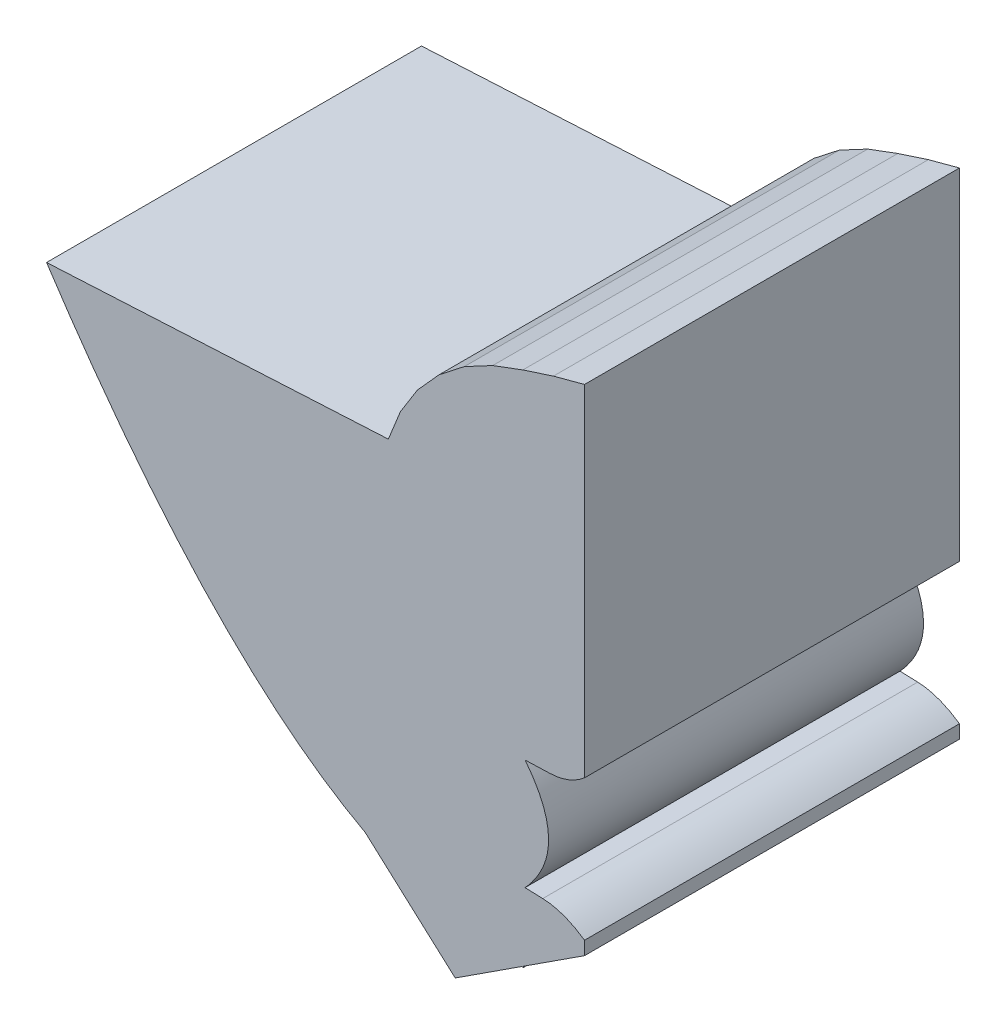
SolidWorks part; units mm, degrees
ref_plane "Alzado" through (0, 0, 0) normal (0, 0, 1) x (1, 0, 0)
ref_plane "Planta" through (0, 0, 0) normal (0, 1, 0) x (1, 0, 0)
ref_plane "Vista lateral" through (0, 0, 0) normal (1, 0, 0) x (0, 0, -1)
sketch "Croquis1" plane through (0, 0, 0) normal (0, 0, 1) x (1, 0, 0)
  line L0 (-8.9818, 12.6082) -> (-23.0359, 11.8716) construction
  line L1 (-8.9818, 12.6082) -> (-23.0359, 11.8716)
  line L2 (-8.9818, 12.6082) -> (-23.0359, 11.8716) construction
  line L3 (-2.1773, 6.1864) -> (-2.1773, -4.6845)
  line L4 (-8.9818, 12.6082) -> (-23.0359, 11.8716)
  line L6 (-1.3949, 1.9763) -> (0.3551, 2.2848) construction
  line L7 (-1.3949, 1.9763) -> (0.3551, 2.2848) construction
  line L8 (0.3551, 2.2848) -> (0.3551, 2.8423) construction
  line L9 (0.3551, 2.2848) -> (0.3551, 3.0015) construction
  line L10 (0.3551, -2.2848) -> (-1.3949, -2.2237) construction
  line L11 (0.3551, -2.2848) -> (-1.3949, -2.2237) construction
  line L12 (0.3551, 2.2848) -> (0.3551, -2.2848) construction
  line L13 (0.3551, -2.2848) -> (0.3551, -2.7233) construction
  line L14 (-8.9818, 12.6082) -> (-6.9949, 10.4774)
  line L15 (-23.0359, 11.5401) -> (-23.0359, 11.8716) construction
  line L16 (-23.0359, 11.5401) -> (-23.0359, 11.8716)
  arc A0 (-18.9452, 7.5409) -> (-23.0359, 11.5401) centre (-69.8841, -40.4718) ccw construction
  arc A1 (-18.9452, 7.5409) -> (-23.0359, 11.5401) centre (-69.8841, -40.4718) ccw
  spline S1 degree 2 poles (-4119.0151, 24659.0515) (3413.1083, -24757.661) (-2705.4818, 24835.5983) knots 0.405517 0.405517 0.405517 0.594449 0.594449 0.594449 weights 1 1 1 only from (-18.9452, 7.5409) to (-2.8466, -5.0591) construction
  spline S2 degree 2 poles (-18.9452, 7.5409) (-10.215, -3.6976) (-2.8466, -5.0591) knots 0.497667 0.497667 0.497667 0.499554 0.499554 0.499554 weights 1 1 1
  spline S3 degree 2 poles (-23607.9882, 8212.1168) (23492.4763, -8550.6979) (-23372.6553, 8887.1675) knots 0.40552 0.40552 0.40552 0.594498 0.594498 0.594498 weights 1 1 1 only from (0.3551, 3.0015) to (-6.9949, 10.4774) construction
  spline S4 degree 2 poles (-2.1773, 6.1864) (-4.0633, 8.1416) (-6.9949, 10.4774) knots 0.501383 0.501383 0.501383 0.502013 0.502013 0.502013 weights 1 1 1
  spline S5 degree 2 poles (-1.3949, -2.2237) (-0.9075, -0.1237) (-1.3949, 1.9763) knots 0 0 0 1 1 1 weights 1 3.231801 1 construction
  spline S6 degree 2 poles (-1.3949, -2.2237) (-0.9075, -0.1237) (-1.3949, 1.9763) knots 0 0 0 1 1 1 weights 1 3.231801 1 construction
  spline S7 degree 2 poles (-24934.0908, 1769.912) (24899.5391, -2178.5787) (-24858.838, 2586.1022) knots 0.405518 0.405518 0.405518 0.594474 0.594474 0.594474 weights 1 1 1 only from (-2.8466, -5.0591) to (0.3551, -2.7233) construction
  spline S8 degree 2 poles (-2.8466, -5.0591) (-2.4982, -4.873) (-2.1773, -4.6845) knots 0.498812 0.498812 0.498812 0.498912 0.498912 0.498912 weights 1 1 1
extrude "croquis base" add sketch "Croquis1" along normal mid plane 13.9874 contours S2 S8 L13 L11 S6 L7 L9 S4 L14 L1 L16 A1 region at (-10.1535, 5.1597, 0)
sketch "Croquis6" plane through (0, 0, 0) normal (1, 0, 0) x (0, 0, -1)
  line L0 (6.9937, 12.6082) -> (6.9937, 10.4774) construction
  line L1 (6.9937, 12.6082) -> (6.9937, -5.0591)
  line L2 (-6.9937, 12.6082) -> (-6.9937, 10.4774) construction
  line L3 (-6.9937, 12.6082) -> (-6.9937, -5.0591)
  line L4 (-6.9937, -5.0591) -> (6.9937, -5.0591) construction
  line L5 (-6.9937, -5.0591) -> (-4.9937, -5.0591)
  line L6 (6.9937, 12.6082) -> (4.9937, -5.0591)
  line L7 (-6.9937, 12.6082) -> (-4.9937, -5.0591)
  line L8 (4.9937, -5.0591) -> (6.9937, -5.0591)
  dimension "D1" = 2
  dimension "D2" = 2
sketch "Croquis9" plane through (0, 0, 0) normal (0, 0, 1) x (1, 0, 0)
  line L0 (0, 0) -> (-4.9559, 0) construction
  line L1 (-2.4454, 0.1046) -> (-1.25, 0) construction
  line L2 (-1.25, 0) -> (-1.25, -4.2203) construction
  line L3 (-2.1773, -1.8404) -> (-2.1773, -4.3883)
  line L4 (-2.1773, 6.1864) -> (-2.1773, -4.6845) construction
  line L5 (-2.4454, 0.1046) -> (-2.0532, -4.3783) construction
  line L6 (-2.4454, 0.1046) -> (-15.184, 3.0892) construction
  line L7 (-19.6099, 15.4015) -> (-15.184, 3.0892) construction
  line L9 (-15.184, 3.0892) -> (-25.9078, 12.6462) construction
  line L10 (-15.184, 3.0892) -> (-13.3572, 5.139) construction
  line L11 (-19.9694, 9.4938) -> (-10.3098, 10)
  line L12 (-10.3098, 10) -> (-2.1773, 6.0829)
  line L13 (-2.1773, 6.0829) -> (-2.1773, 2.4242)
  line L15 (-2.1773, 6.1864) -> (-2.1773, -4.6845) construction
  parabola Q0 (-2.1773, 2.4242) -> (-2.1773, -1.8404) focus (-2.4454, 0.1046) apex (-1.25, 0)
  parabola Q1 (-2.1773, -4.3883) -> (-19.9694, 9.4938) focus (-2.4454, 0.1046) apex (-2.0532, -4.3783)
  spline S0 degree 2 poles (-18.9452, 7.5409) (-10.215, -3.6976) (-2.8466, -5.0591) knots 0.497667 0.497667 0.497667 0.499554 0.499554 0.499554 weights 1 1 1 construction
  dimension "D1" = 95
  dimension "D2" = 1.25
  dimension "D3" = 1.2
  dimension "D4" = 4.5
  dimension "D5" = 5
  dimension "D6" = 3
  dimension "D7" = 10
extrude "lente ppal 1" add sketch "Croquis9" along normal up to surface and the other way up to surface contours Q1 L3 Q0 L13 L12 L11 region at (-9.1064, 3.5992, 0) up to face at (-11.7662, 6.8113, 6.9937) other way up to face at (-11.7662, 6.8113, -6.9937)
extrude "lente ppal 2" cut sketch "Croquis9<3>" against normal through all both and the other way through all flip side to cut
sketch "Croquis9<3>" plane through (0, 0, 0) normal (0, 0, 1) x (1, 0, 0) same geometry as "Croquis9"
sketch "Croquis8" plane through (0, 0, 0) normal (0, 0, 1) x (1, 0, 0)
  line L0 (-8.9818, 12.6082) -> (-23.0359, 11.8716) construction
  line L1 (-10.3098, 10) -> (0.1, 15.5879) construction
  line L3 (0.1, 2.8777) -> (0.1, 15.5879)
  line L5 (-7.2179, 10.162) -> (-6.7684, 11.2747)
  line L6 (-6.7684, 11.2747) -> (-6.1325, 12.2923)
  line L7 (-6.1325, 12.2923) -> (-5.3295, 13.1841)
  line L8 (-5.3295, 13.1841) -> (-4.3839, 13.9229)
  line L9 (-4.3839, 13.9229) -> (-3.3244, 14.4863)
  line L10 (-3.3244, 14.4863) -> (-2.2004, 14.9065)
  line L11 (-2.2004, 14.9065) -> (-1.0591, 15.2773)
  line L12 (-1.0591, 15.2773) -> (0.1, 15.5879)
  line L13 (-0.5, 2) -> (-9.2621, 13.0152) construction
  line L14 (-9.2621, 13.0152) -> (-9.6721, 13.4466) construction
  line L15 (-9.2621, 13.0152) -> (-9.8313, 13.8617) construction
  line L16 (-0.5, 2) -> (-6.9932, 10.7183) construction
  line L17 (-6.9932, 10.7183) -> (-9.8657, 11.8789) construction
  line L18 (-0.5, 2) -> (-6.4504, 11.7835) construction
  line L19 (-1.1905, 2.3769) -> (-13.6677, 1.9412) construction
  line L20 (-6.4504, 11.7835) -> (-8.5297, 13.0828) construction
  line L21 (-0.5, 2) -> (-5.731, 12.7382) construction
  line L22 (-0.5, 2) -> (-4.8567, 13.5535) construction
  line L23 (-4.8567, 13.5535) -> (-7.2264, 16.5865) construction
  line L24 (-0.5, 2) -> (-3.8542, 14.2046) construction
  line L25 (-3.8542, 14.2046) -> (-5.6175, 17.521) construction
  line L26 (-0.5, 2) -> (-2.7624, 14.6964) construction
  line L27 (-2.7624, 14.6964) -> (-4.1395, 18.3795) construction
  line L28 (-0.5, 2) -> (-1.6297, 15.0919) construction
  line L29 (-1.6297, 15.0919) -> (-2.365, 17.3548) construction
  line L30 (-0.5, 2) -> (-0.4796, 15.4326) construction
  line L31 (-0.4796, 15.4326) -> (-1.0837, 17.6873) construction
  line L32 (-6.4504, 11.7835) -> (-9.194, 13.4978) construction
  line L33 (-5.731, 12.7382) -> (-8.3325, 15.0806) construction
  line L34 (-10.3098, 10) -> (-10.3098, 19.2428) construction
  line L35 (-0.4796, 15.4326) -> (-1.3923, 18.839) construction
  line L36 (-10.3098, 10) -> (-7.2179, 10.162)
  line L37 (-6.9932, 10.7183) -> (-7.7178, 13.8573) construction
  line L38 (-6.9932, 10.7183) -> (-7.6851, 10.9979) construction
  line L39 (-6.4504, 11.7835) -> (-7.328, 15.5847) construction
  line L40 (-6.4504, 11.7835) -> (-8.1247, 12.8297) construction
  line L41 (-5.731, 12.7382) -> (-6.4786, 15.9764) construction
  line L42 (-5.731, 12.7382) -> (-7.1919, 14.0536) construction
  line L43 (-4.8567, 13.5535) -> (-5.8037, 17.6554) construction
  line L44 (-4.8567, 13.5535) -> (-6.0786, 15.1174) construction
  line L45 (-3.8542, 14.2046) -> (-4.8235, 18.4032) construction
  line L46 (-3.8542, 14.2046) -> (-4.9673, 16.2982) construction
  line L47 (-2.7624, 14.6964) -> (-3.6965, 18.7423) construction
  line L48 (-2.7624, 14.6964) -> (-3.4418, 16.5134) construction
  line L49 (-0.5, 2) -> (-0.5437, 2.5) construction
  line L50 (-0.5437, 2.5) -> (-0.8858, 3.4397) construction
  line L51 (0, 0) -> (0, 1.5958) construction
  line L52 (0, 12.6082) -> (0, -5.0591) construction
  line L53 (-1.6297, 15.0919) -> (-2.8173, 18.7468) construction
  line L54 (-1.6297, 15.0919) -> (-2.2911, 17.9567) construction
  line L55 (-0.4796, 15.4326) -> (-1.0428, 17.8722) construction
  line L56 (-10.3098, 10) -> (-2.1773, 2.3425)
  line L57 (-2.1773, 2.3425) -> (-1.1905, 2.3769)
  line L58 (-10.3098, 10) -> (-19.9694, 9.4938) construction
  line L60 (-2.1773, 6.0829) -> (-10.3098, 10) construction
  parabola Q0 (-1.1905, 2.3769) -> (0.1, 2.8777) focus (-0.8858, 3.4397) apex (-0.5437, 2.5)
  spline S1 degree 2 poles (-10.3098, 10) (-2.4445, 4.1882) (-0.2283, 0.4324) knots 0.500548 0.500548 0.500548 0.502013 0.502013 0.502013 weights 1 1 1 construction
  dimension "D1" = 5.039
  dimension "D3" = 15
  dimension "D4" = 25
  dimension "D5" = 80
  dimension "D6" = 45
  dimension "D7" = 35
  dimension "D8" = 7.5
  dimension "D9" = 5
  dimension "D10" = 55
  dimension "D11" = 211.322
  dimension "D12" = 206.691
  dimension "D13" = 202.027
  dimension "D14" = 197.339
  dimension "D15" = 192.633
  dimension "D16" = 0.5
  dimension "D17" = 0.5
  dimension "D18" = 2
  dimension "D19" = 5
  dimension "D20" = 20
  dimension "D21" = 88
  dimension "D22" = 1
  dimension "D23" = 0.1
  dimension "D24" = 178
  dimension "D25" = 1.2
  dimension "D26" = 10
extrude "lente frontal" add sketch "Croquis8" along normal up to surface and the other way up to surface up to face at (-5.0154, 2.8272, 6.9937) other way up to face at (-7.9808, 4.4301, -6.9937)
sketch "Croquis11" plane through (0, 0, 0) normal (0, 0, 1) x (1, 0, 0)
  line L0 (0, 0) -> (0, -3.4622) construction
  line L1 (0, 0) -> (3.4097, 0) construction
  line L2 (0, 0) -> (-1.5, -1.8) construction
  line L4 (-1.5209, -2.9998) -> (-1.5, -1.8) construction
  line L5 (-1.4581, -1.8011) -> (-2.5935, -1.7614) construction
  line L7 (0.1, -2.3678) -> (0.1, -2.8678)
  line L8 (0.1, 2.8777) -> (0.1, 15.5879) construction
  line L14 (-1.4581, -1.8011) -> (-9.7064, -1.5131)
  line L15 (-9.7064, -1.5131) -> (-4.7232, -6)
  line L16 (-4.7232, -6) -> (-4.7232, 3.7291) construction
  line L17 (0.1, -2.8678) -> (-4.7232, -6)
  parabola Q0 (-1.4581, -1.8011) -> (0.1, -2.3678) focus (-1.5209, -2.9998) apex (-1.5, -1.8)
  dimension "D1" = 1.8
  dimension "D2" = 88
  dimension "D3" = 1.2
  dimension "D4" = 1.5
  dimension "D5" = 1
  dimension "D6" = 0.5
  dimension "D7" = 6
  dimension "D9" = 105
  dimension "D10" = 57
extrude "lente trasera" add sketch "Croquis11" along normal up to surface and the other way up to surface up to face at (-3.7041, 8.4573, 6.9937) other way up to face at (-4.8085, 9.1371, -6.9937)
